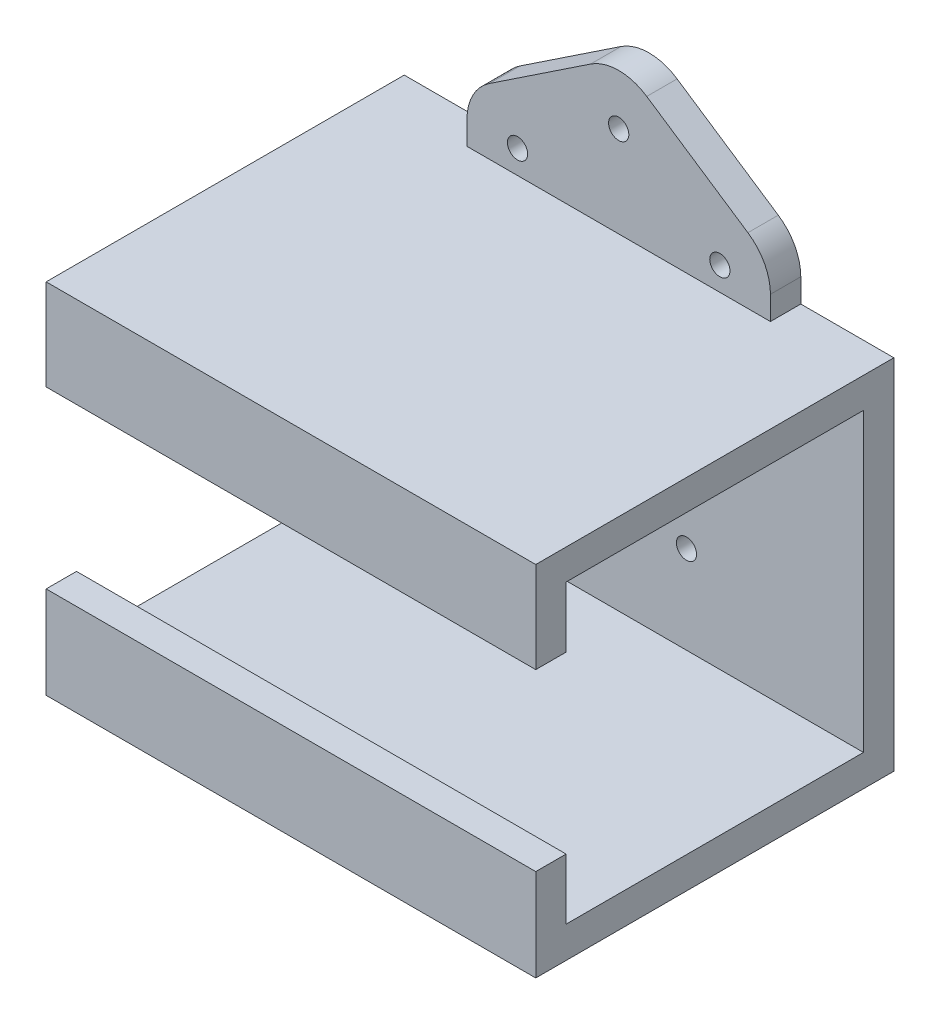
SolidWorks part; units mm, degrees
ref_plane "Front Plane" through (0, 0, 0) normal (0, 0, 1) x (1, 0, 0)
ref_plane "Top Plane" through (0, 0, 0) normal (0, 1, 0) x (1, 0, 0)
ref_plane "Right Plane" through (0, 0, 0) normal (1, 0, 0) x (0, 0, -1)
sketch "Sketch4" plane through (0, 0, 0) normal (0, 0, 1) x (1, 0, 0)
  line L1 (-43.4263, 3.8686) -> (4.9737, 3.8686)
  line L2 (-43.4263, 3.8686) -> (-43.4263, -31.5314)
  line L3 (-43.4263, -31.5314) -> (4.9737, -31.5314)
  line L4 (4.9737, 3.8686) -> (4.9737, -31.5314)
extrude "Bottom_Plate" add sketch "Sketch4" along normal blind 3
sketch "Sketch5" plane through (0, 0, 3) normal (0, 0, 1) x (1, 0, 0)
  line L0 (4.9737, -31.5314) -> (4.9737, 3.8686) construction
  line L1 (-43.4263, 3.8686) -> (4.9737, 3.8686)
  line L2 (-43.4263, 3.8686) -> (-43.4263, 0.8686)
  line L3 (-43.4263, 0.8686) -> (4.9737, 0.8686)
  line L4 (4.9737, 3.8686) -> (4.9737, 0.8686)
  line L6 (-43.4263, -31.5314) -> (4.9737, -31.5314)
  line L7 (-43.4263, -31.5314) -> (-43.4263, -28.4198)
  line L8 (-43.4263, -28.4198) -> (4.9737, -28.4198)
  line L9 (4.9737, -31.5314) -> (4.9737, -28.4198)
extrude "Side_Plate" add sketch "Sketch5" along normal blind 32.4 contours L2 L1 L4 L3 | L7 L6 L9 L8
sketch "Sketch6" plane through (0, 0.8686, 0) normal (0, -1, 0) x (1, 0, 0)
  line L0 (4.9737, 35.4) -> (4.9737, 3) construction
  line L1 (-43.4263, 35.4) -> (4.9737, 35.4)
  line L2 (-43.4263, 35.4) -> (-43.4263, 32.4)
  line L3 (-43.4263, 32.4) -> (4.9737, 32.4)
  line L4 (4.9737, 35.4) -> (4.9737, 32.4)
extrude "Top_Plate_1" add sketch "Sketch6" along normal blind 6
sketch "Sketch7" plane through (0, -28.4198, 0) normal (0, 1, 0) x (1, 0, 0)
  line L0 (-43.4263, -35.4) -> (-43.4263, -3) construction
  line L1 (4.9737, -35.4) -> (-43.4263, -35.4)
  line L2 (4.9737, -35.4) -> (4.9737, -32.4)
  line L3 (4.9737, -32.4) -> (-43.4263, -32.4)
  line L4 (-43.4263, -35.4) -> (-43.4263, -32.4)
extrude "Top_Plate_2" add sketch "Sketch7" along normal blind 6
sketch "Sketch8" plane through (0, 0, 3) normal (0, 0, 1) x (1, 0, 0)
  circle A0 centre (-34.5263, -19.7198) radius 1
  circle A1 centre (-34.6119, -7.8314) radius 1
  circle A2 centre (-12.6119, -7.8357) radius 1
  circle A3 centre (-12.5263, -19.7198) radius 1
  point P5 (-34.5263, -19.7198)
  point P13 (-34.6119, -7.8314)
  point P20 (-12.6119, -7.8357)
  point P21 (-12.5263, -19.7198)
  dimension "D3" = 22
  dimension "D4" = 22
extrude "Camera_Screw_Holes" cut sketch "Sketch8" against normal up to next
sketch "Sketch10" plane through (0, 0, 0) normal (0, 0, -1) x (-1, 0, 0)
  line L0 (-4.9737, 3.8686) -> (-4.9737, 17.8686) construction
  line L1 (-4.9737, 17.8686) -> (43.4263, 17.8686) construction
  line L2 (43.4263, 17.8686) -> (43.4263, 3.8686) construction
  line L3 (4.2263, 3.8686) -> (4.2263, 6.2019)
  line L4 (-4.9737, 3.8686) -> (43.4263, 3.8686) construction
  line L5 (34.2263, 3.8686) -> (34.2263, 6.2019)
  line L6 (6.4528, 10.3622) -> (16.4528, 17.0289)
  line L7 (21.9998, 17.0289) -> (31.9998, 10.3622)
  line L12 (6.4528, -38.025) -> (16.4528, -44.6916)
  line L13 (21.9998, -44.6916) -> (31.9998, -38.025)
  line L14 (34.2263, -31.5314) -> (34.2263, -33.8647)
  line L15 (4.2263, -31.5314) -> (4.2263, -33.8647)
  arc A0 (16.4528, 17.0289) -> (21.9998, 17.0289) centre (19.2263, 12.8686) cw
  arc A1 (31.9998, 10.3622) -> (34.2263, 6.2019) centre (29.2263, 6.2019) cw
  arc A2 (6.4528, 10.3622) -> (4.2263, 6.2019) centre (9.2263, 6.2019) ccw
  circle A3 centre (19.2263, 12.8686) radius 1
  circle A4 centre (9.2263, 6.2019) radius 1
  circle A5 centre (29.2263, 6.2019) radius 1
  arc A9 (16.4528, -44.6916) -> (21.9998, -44.6916) centre (19.2263, -40.5314) ccw
  circle A10 centre (29.2263, -33.8647) radius 1
  circle A11 centre (9.2263, -33.8647) radius 1
  circle A12 centre (19.2263, -40.5314) radius 1
  arc A13 (6.4528, -38.025) -> (4.2263, -33.8647) centre (9.2263, -33.8647) cw
  arc A14 (31.9998, -38.025) -> (34.2263, -33.8647) centre (29.2263, -33.8647) ccw
  point P12 (19.2263, 17.8686)
  point P22 (19.2263, 17.8686)
  line M14 (43.4263, 3.8686) -> (-4.9737, 3.8686)
  line M16 (-4.9737, -31.5314) -> (43.4263, -31.5314)
  dimension "D2" = 9.2
  dimension "D3" = 14
  dimension "D1" = 30
extrude "Case_Attachment_1" add sketch "Sketch10" against normal blind 3 contours L6 A2 L3 L5 A1 L7 A0 A5 A4 A3 M14 region at (-19.2263, 9.2626, 0)
extrude "Case_Attachment_2" add sketch "Sketch10<4>" against normal blind 3 contours L13 A14 L14 L15 A13 L12 A9 A12 A10 A11 M16 region at (-19.2263, -36.9254, 0)
sketch "Sketch10<4>" plane through (0, 0, 0) normal (0, 0, -1) x (-1, 0, 0) same geometry as "Sketch10"
